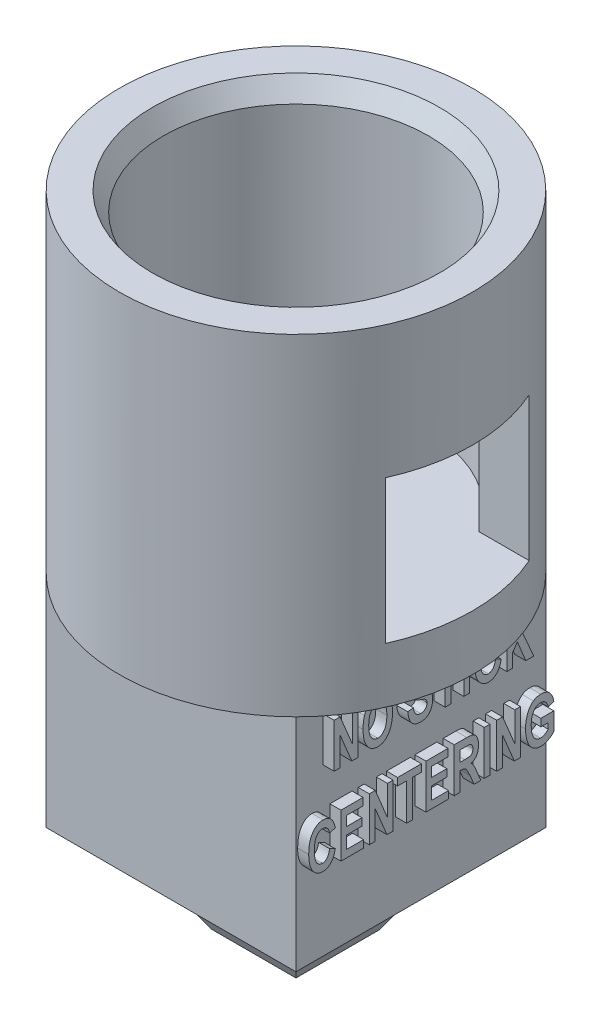
SolidWorks part; units mm, degrees
ref_plane "Спереди" through (0, 0, 0) normal (0, 0, 1) x (1, 0, 0)
ref_plane "Сверху" through (0, 0, 0) normal (0, 1, 0) x (1, 0, 0)
ref_plane "Справа" through (0, 0, 0) normal (1, 0, 0) x (0, 0, -1)
sketch "Sketch1" plane through (0, 0, 0) normal (0, 1, 0) x (1, 0, 0)
  line L1 (4.8, -4.8) -> (-4.8, -4.8)
  line L2 (4.8, -4.8) -> (4.8, 4.8)
  line L3 (4.8, 4.8) -> (-4.8, 4.8)
  line L4 (-4.8, -4.8) -> (-4.8, 4.8)
  line L5 (4.8, -4.8) -> (-4.8, 4.8) construction
  line L6 (4.8, 4.8) -> (-4.8, -4.8) construction
  point P0 (0, 0)
  dimension "D1" = 9.6
extrude "Boss-Extrude1" add sketch "Sketch1" along normal blind 28
sketch "Sketch2" plane through (0, 28, 0) normal (0, 1, 0) x (1, 0, 0)
  circle A0 centre (0, 0) radius 16
  dimension "D1" = 32
extrude "Boss-Extrude2" add sketch "Sketch2" along normal blind 30
sketch "Sketch3" plane through (0, 58, 0) normal (0, 1, 0) x (1, 0, 0)
  circle A0 centre (0, 0) radius 12
  dimension "D1" = 24
extrude "Cut-Extrude1" cut sketch "Sketch3" against normal blind 25
chamfer "Chamfer1" distance 1 angle 60 4 edges at (4.8, 0, 0) (0, 0, -4.8) (-4.8, 0, 0) (0, 0, 4.8)
chamfer "Chamfer2" distance 1 angle 60 1 edges at (0, 58, 12)
sketch "Sketch4" plane through (0, 28, 0) normal (0, -1, 0) x (1, 0, 0)
  line L1 (-11.3137, 11.3137) -> (11.3137, 11.3137)
  line L2 (-11.3137, 11.3137) -> (-11.3137, -11.3137)
  line L3 (-11.3137, -11.3137) -> (11.3137, -11.3137)
  line L4 (11.3137, 11.3137) -> (11.3137, -11.3137)
  line L5 (-11.3137, 11.3137) -> (11.3137, -11.3137) construction
  line L6 (-11.3137, -11.3137) -> (11.3137, 11.3137) construction
  line L7 (-7.75, 7.75) -> (7.75, 7.75)
  line L8 (-7.75, 7.75) -> (-7.75, -7.75)
  line L9 (-7.75, -7.75) -> (7.75, -7.75)
  line L10 (7.75, 7.75) -> (7.75, -7.75)
  line L11 (-7.75, 7.75) -> (7.75, -7.75) construction
  line L12 (-7.75, -7.75) -> (7.75, 7.75) construction
  circle A0 centre (0, 0) radius 16 construction
  point P0 (0, 0)
  point P9 (0, 0)
  dimension "D1" = 15.5
extrude "Boss-Extrude3" add sketch "Sketch4" along normal blind 20
sketch "Sketch6" plane through (-11.3137, 0, 0) normal (-1, 0, 0) x (0, 0, 1)
  line L0 (-11.3137, 23) -> (11.3137, 23) construction
  line L1 (-11.3137, 8) -> (-11.3137, 28) construction
  line L2 (11.3137, 8) -> (11.3137, 28) construction
  line L3 (11.3137, 28) -> (-11.3137, 28) construction
  text T0 "REMOVE\r\n  AFTER\r\n  FLIGHT" font "Arial" height 4
  dimension "D1" = 5
extrude "Boss-Extrude4" add sketch "Sketch6" along normal blind 1
sketch "Sketch7" plane through (11.3137, 0, 0) normal (1, 0, 0) x (0, 0, -1)
  line L0 (-11.3137, 23) -> (11.3137, 23) construction
  line L1 (-11.3137, 8) -> (-11.3137, 28) construction
  line L2 (11.3137, 8) -> (11.3137, 28) construction
  line L3 (11.3137, 28) -> (-11.3137, 28) construction
  text T0 "<b>  NO STICK</b>\r\n<b>CENTERING</b>" font "Arial" height 4
  dimension "D1" = 5
extrude "Boss-Extrude5" add sketch "Sketch7" along normal blind 1
sketch "Sketch8" plane through (0, 33, 0) normal (0, 1, 0) x (1, 0, 0)
  line L0 (12, 0) -> (-12, 0) construction
  line L2 (5.5, -6.5) -> (18.5, -6.5)
  line L3 (5.5, -6.5) -> (5.5, 6.5)
  line L4 (5.5, 6.5) -> (18.5, 6.5)
  line L5 (18.5, -6.5) -> (18.5, 6.5)
  line L6 (5.5, -6.5) -> (18.5, 6.5) construction
  line L7 (5.5, 6.5) -> (18.5, -6.5) construction
  circle A2 centre (0, 0) radius 12 construction
  point P9 (12, 0)
  dimension "D1" = 13
extrude "Cut-Extrude2" cut sketch "Sketch8" along normal blind 13
chamfer "Chamfer3" distance 4 angle 50 1 edges at (12, 46, 0)
